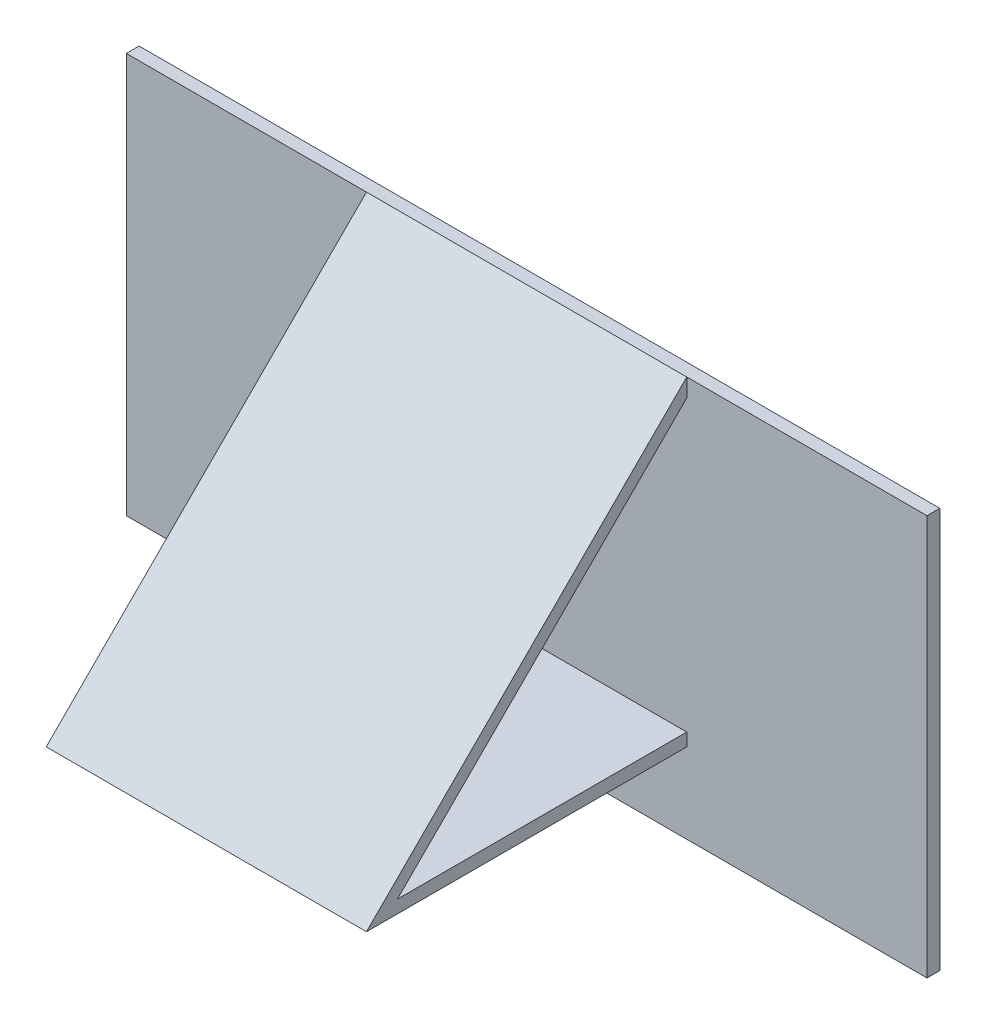
SolidWorks part; units mm, degrees
ref_plane "Ebene vorne" through (0, 0, 0) normal (0, 0, 1) x (1, 0, 0)
ref_plane "Ebene oben" through (0, 0, 0) normal (0, 1, 0) x (1, 0, 0)
ref_plane "Ebene rechts" through (0, 0, 0) normal (1, 0, 0) x (0, 0, -1)
sketch "Skizze1" plane through (0, 0, 0) normal (0, 0, 1) x (1, 0, 0)
  line L1 (0, 125) -> (250, 125)
  line L2 (0, 125) -> (0, 0)
  line L3 (0, 0) -> (250, 0)
  line L4 (250, 125) -> (250, 0)
  dimension "D1" = 250
  dimension "D2" = 125
extrude "Aufsatz-Linear austragen1" add sketch "Skizze1" along normal blind 4 contours L2 L1 L4 L3
sketch "Skizze2" plane through (0, 0, 4) normal (0, 0, 1) x (1, 0, 0)
  line L0 (75, 75) -> (0, 75) construction
  line L1 (75, 125) -> (175, 125)
  line L2 (75, 125) -> (75, 25)
  line L3 (75, 25) -> (175, 25)
  line L4 (175, 125) -> (175, 25)
  line L5 (0, 125) -> (0, 0) construction
  line L6 (175, 75) -> (250, 75) construction
  line L7 (250, 125) -> (250, 0) construction
  line L8 (0, 125) -> (250, 125) construction
  point P20 (0, 0)
  dimension "D1" = 100
  dimension "D2" = 100
extrude "Aufsatz-Linear austragen2" add sketch "Skizze2" along normal blind 100
sketch "Skizze3" plane through (75, 0, 0) normal (-1, 0, 0) x (0, 0, 1)
  line L0 (104, 25) -> (104, 125)
  line L1 (104, 125) -> (4, 125)
  line L2 (4, 125) -> (104, 25)
extrude "Schnitt-Linear austragen1" cut sketch "Skizze3" against normal blind 100
sketch "Skizze4" plane through (75, 0, 0) normal (-1, 0, 0) x (0, 0, 1)
  line L0 (4, 119.3431) -> (94.3431, 29)
  line L1 (94.3431, 29) -> (4, 29)
  line L2 (4, 29) -> (4, 119.3431)
  line L3 (4, 125) -> (104, 25) construction
  line L5 (104, 25) -> (4, 25) construction
  line L6 (4, 125) -> (4, 25) construction
  dimension "D1" = 4
  dimension "D3" = 4
extrude "Schnitt-Linear austragen2" cut sketch "Skizze4" against normal blind 100 contours L2 L0 L1
